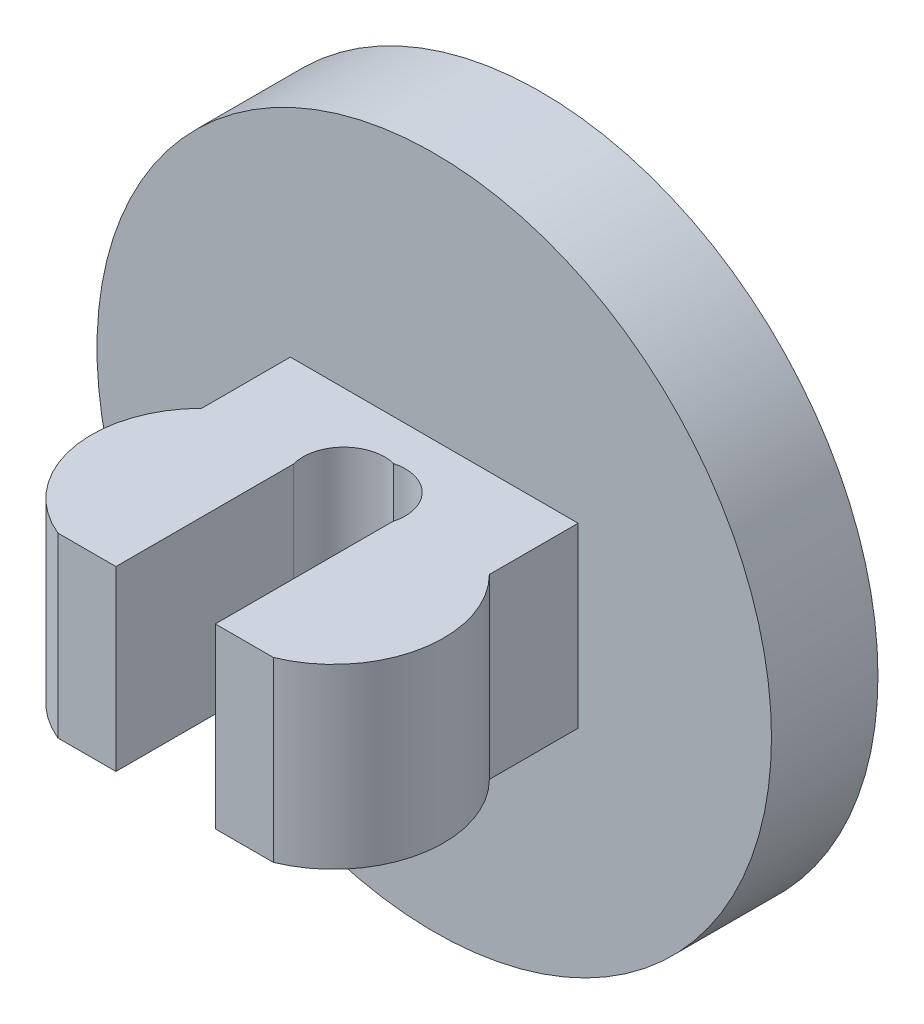
SolidWorks part; units mm, degrees
ref_plane "Front Plane" through (0, 0, 0) normal (0, 0, 1) x (1, 0, 0)
ref_plane "Top Plane" through (0, 0, 0) normal (0, 1, 0) x (1, 0, 0)
ref_plane "Right Plane" through (0, 0, 0) normal (1, 0, 0) x (0, 0, -1)
sketch "Sketch1" plane through (0, 0, 0) normal (0, 0, 1) x (1, 0, 0)
  circle A0 centre (0, 0) radius 9.5
  dimension "D1" = 19
extrude "Boss-Extrude1" add sketch "Sketch1" along normal blind 3
sketch "Sketch3" plane through (0, 0, 0) normal (0, 1, 0) x (1, 0, 0)
  line L0 (-9.5, -3) -> (9.5, -3) construction
  line L1 (0, 0) -> (0, -14.3724) construction
  line L8 (-4.053, -5.5) -> (-4.053, -3)
  line L11 (-3.0361, -10.5668) -> (-1.4, -10.5668)
  line L12 (-1.4, -10.5668) -> (-1.4, -5.5668)
  line L13 (-4.053, -3) -> (4.053, -3)
  line L14 (1.4, -10.5668) -> (1.4, -5.5668)
  line L15 (3.0361, -10.5668) -> (1.4, -10.5668)
  line L16 (4.053, -5.5) -> (4.053, -3)
  arc A8 (-1.4, -5.5668) -> (0, -4.1424) centre (-0.289, -5.2586) cw
  arc A10 (-3.0361, -10.5668) -> (-4.053, -5.5) centre (-1.8537, -7.6941) cw
  arc A11 (3.0361, -10.5668) -> (4.053, -5.5) centre (1.8537, -7.6941) ccw
  arc A12 (1.4, -5.5668) -> (0, -4.1424) centre (0.289, -5.2586) ccw
  point P21 (0, -3)
  point P25 (0, -3)
  dimension "D5" = 3.1066
  dimension "D8" = 1.153
  dimension "D1" = 2.653
  dimension "D2" = 1.4
  dimension "D3" = 1.6361
  dimension "D4" = 5.0668
  dimension "D6" = 5
  dimension "D7" = 1.4244
  dimension "D9" = 2.5
extrude "Boss-Extrude2" add sketch "Sketch3" along normal mid plane 5
sketch "Sketch4" plane through (0, 0, 0) normal (0, 1, 0) x (1, 0, 0)
  line L0 (-4.9603, -7.6941) -> (0, -7.6941) construction
  line L1 (-1.4, -10.5668) -> (-1.4, -5.5668) construction
  line L3 (-4.053, -3) -> (0, -3) construction
  line L4 (4.053, -3) -> (-4.053, -3) construction
  line L5 (-3.0361, -10.5668) -> (-1.4, -10.5668) construction
  arc A0 (-4.053, -5.5) -> (-3.0361, -10.5668) centre (-1.8537, -7.6941) ccw construction
  dimension "D1" = 4.9603
  dimension "D2" = 7.5668
  dimension "D3" = 1.4
